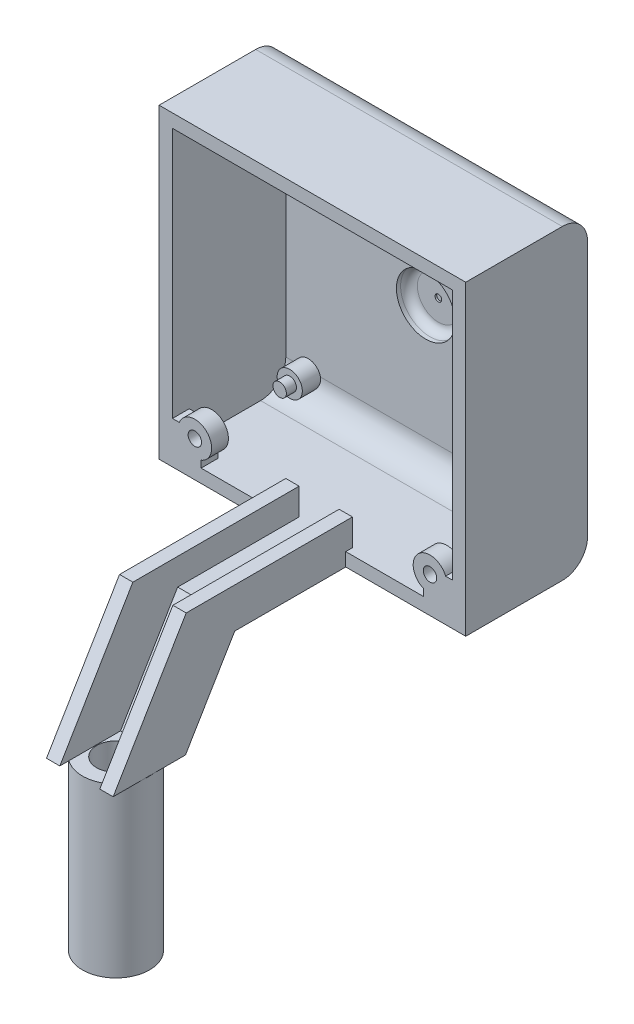
SolidWorks part; units mm, degrees
ref_plane "Front Plane" through (0, 0, 0) normal (0, 0, 1) x (1, 0, 0)
ref_plane "Top Plane" through (0, 0, 0) normal (0, 1, 0) x (1, 0, 0)
ref_plane "Right Plane" through (0, 0, 0) normal (1, 0, 0) x (0, 0, -1)
sketch "Sketch1" plane through (0, 0, 0) normal (0, 0, 1) x (1, 0, 0)
  line L0 (0, 0) -> (0, -36.5125)
  line L1 (0, -36.5125) -> (36.5125, -36.5125)
  line L2 (36.5125, -36.5125) -> (36.5125, 0)
  line L3 (36.5125, 0) -> (0, 0)
  dimension "D1" = 36.5125
extrude "Extrude1" add sketch "Sketch1" along normal blind 1
sketch "Sketch2" plane through (0, 0, 1) normal (0, 0, 1) x (1, 0, 0)
  line L0 (1.5875, -1.5875) -> (34.925, -1.5875)
  line L3 (34.925, -34.925) -> (34.925, -1.5875)
  line L4 (1.5875, -34.925) -> (1.5875, -1.5875)
  line L5 (34.925, -34.925) -> (1.5875, -34.925)
  line L6 (0, 0) -> (36.5125, 0)
  line L7 (36.5125, -36.5125) -> (36.5125, 0) construction
  line L8 (36.5125, 0) -> (0, 0) construction
  line L9 (36.5125, 0) -> (36.5125, -36.5125)
  line L10 (0, -36.5125) -> (36.5125, -36.5125) construction
  line L11 (36.5125, -36.5125) -> (0, -36.5125)
  line L12 (0, 0) -> (0, -36.5125) construction
  line L13 (0, -36.5125) -> (0, 0)
extrude "Extrude2" add sketch "Sketch2" along normal blind 13.5
fillet "Fillet7" radius 3 4 edges at (18.2562, 0, 0) (18.2562, -36.5125, 0) (18.2562, -1.5875, 1) (18.2562, -34.925, 1)
sketch "Sketch5" plane through (0, 0, 1) normal (0, 0, 1) x (1, 0, 0)
  line L0 (1.5875, -1.5875) -> (34.925, -34.925) construction
  line L1 (34.925, -1.5875) -> (1.5875, -34.925) construction
  line L2 (34.925, -34.925) -> (34.925, -1.5875) construction
  circle A0 centre (4.2562, -4.2562) radius 1.5
  circle A1 centre (32.2563, -4.2562) radius 1.5
  circle A2 centre (4.2562, -32.2563) radius 1.5
  circle A3 centre (32.2563, -32.2563) radius 1.5
  point P8 (4.2562, -32.2563)
  point P9 (18.2562, -18.2562)
  point P10 (32.2563, -32.2563)
  point P11 (4.2562, -4.2562)
  point P12 (32.2563, -4.2562)
  dimension "D1" = 14
  dimension "D2" = 14
  dimension "D3" = 14
  dimension "D4" = 14
extrude "Extrude5" add sketch "Sketch5" along normal blind 2.2
sketch "Sketch6" plane through (0, 0, 3.2) normal (0, 0, 1) x (1, 0, 0)
  circle A0 centre (4.2562, -32.2563) radius 0.8
  circle A1 centre (32.2563, -32.2563) radius 0.8
  circle A2 centre (4.2562, -4.2562) radius 0.8
  circle A3 centre (32.2563, -4.2562) radius 0.8
extrude "Extrude6" add sketch "Sketch6" along normal blind 1.2
sketch "Sketch7" plane through (0, 0, 1) normal (0, 0, 1) x (1, 0, 0)
  line L0 (0, 0) -> (36.5125, -36.5125) construction
  line L1 (36.5125, 0) -> (0, -36.5125) construction
  line L2 (0, -36.5125) -> (36.5125, -36.5125) construction
  circle A0 centre (18.2562, -18.2562) radius 4.5
  point P9 (18.2562, -18.2562)
extrude "Extrude7" add sketch "Sketch7" against normal blind 2.5
sketch "Sketch8" plane through (0, 0, 1) normal (0, 0, 1) x (1, 0, 0)
  line L0 (0, 0) -> (36.5125, -36.5125) construction
  line L1 (36.5125, 0) -> (0.5068, -36.3499) construction
  circle A0 centre (18.2562, -18.2562) radius 3.5
  point P6 (18.3431, -18.3431)
extrude "Extrude9" cut sketch "Sketch8" against normal blind 1.5
fillet "Fillet8" radius 1 1 edges at (22.7562, -18.2562, -1.5)
fillet "Fillet10" radius 1 1 edges at (21.7562, -18.2562, -0.5)
sketch "Sketch9" plane through (0, 0, -0.5) normal (0, 0, 1) x (1, 0, 0)
  circle A0 centre (18.2562, -18.2562) radius 0.4
extrude "Extrude10" cut sketch "Sketch9" against normal blind 0.2
sketch "Sketch10" plane through (0, 0, 14.5) normal (0, 0, 1) x (1, 0, 0)
  line L0 (-4.7625, -31.5125) -> (46.0375, -31.5125) construction
  line L1 (5, -15.875) -> (5, -49.2125) construction
  line L2 (31.5125, -15.875) -> (31.5125, -49.2125) construction
  line L3 (31.5125, -34.1128) -> (31.5125, -36.5126)
  line L4 (31.5125, -36.5126) -> (36.5125, -36.5125)
  line L5 (36.5125, -36.5125) -> (36.5125, -31.5125)
  line L6 (36.5125, -36.5125) -> (36.5125, 0) construction
  line L7 (36.5125, -31.5125) -> (34.1128, -31.5125)
  line L8 (2.3997, -31.5125) -> (0, -31.5125)
  line L9 (0, 0) -> (0, -36.5125) construction
  line L10 (0, -31.5125) -> (0, -36.5125)
  line L11 (0, -36.5125) -> (5, -36.5125)
  line L12 (0, -36.5125) -> (36.5125, -36.5125) construction
  line L13 (5, -36.5125) -> (5, -34.1128)
  circle A0 centre (4.2562, -32.2563) radius 2 construction
  circle A1 centre (32.2563, -32.2563) radius 2 construction
  circle A2 centre (4.2562, -32.2563) radius 0.8
  circle A3 centre (32.2563, -32.2563) radius 0.8
  arc A4 (2.3997, -31.5125) -> (5, -34.1128) centre (4.2562, -32.2563) cw
  arc A5 (34.1128, -31.5125) -> (31.5125, -34.1128) centre (32.2563, -32.2563) ccw
  dimension "D1" = 5
  dimension "D2" = 5
  dimension "D3" = 5
extrude "Extrude11" add sketch "Sketch10" against normal blind 2
sketch "Sketch11" plane through (0, 0, 14.5) normal (0, 0, 1) x (1, 0, 0)
  line L0 (14.2875, -36.5125) -> (14.2875, -31.75)
  line L1 (14.2875, -31.75) -> (15.875, -31.75)
  line L2 (22.225, -31.75) -> (22.225, -36.5125)
  line L3 (0, -36.5125) -> (31.5125, -36.5125) construction
  line L4 (22.225, -36.5125) -> (14.2875, -36.5125)
  line L5 (15.875, -31.75) -> (15.875, -33.3375)
  line L6 (20.6375, -33.3375) -> (20.6375, -34.925)
  line L7 (34.925, -34.925) -> (1.5875, -34.925) construction
  line L8 (20.6375, -34.925) -> (15.875, -34.925)
  line L9 (5, -34.925) -> (31.5125, -34.925) construction
  line L10 (15.875, -33.3375) -> (15.875, -34.925)
  line L11 (22.225, -31.75) -> (20.6375, -31.75)
  line L12 (20.6375, -31.75) -> (20.6375, -33.3375)
  point P0 (4.2562, -32.2563)
  point P1 (32.2563, -32.2563)
extrude "Extrude12" add sketch "Sketch11" along normal blind 19 and the other way blind 0.8
sketch "Sketch13" plane through (14.2875, 0, 0) normal (-1, 0, 0) x (0, 0, 1)
  line L0 (33.5, -31.75) -> (25.5, -36.5125)
  line L1 (14.5, -36.5125) -> (33.5, -36.5125) construction
  line L2 (25.5, -36.5125) -> (33.5, -36.5125)
  line L3 (33.5, -36.5125) -> (33.5, -31.75)
extrude "Extrude13" cut sketch "Sketch13" against normal through all
sketch "Sketch14" plane through (0, -38.1668, 22.7212) normal (0, -0.8593, 0.5115) x (1, 0, 0)
  line L0 (22.225, 12.5443) -> (22.225, 5.1443)
  line L1 (15.875, 12.5443) -> (14.2875, 12.5443) construction
  line L2 (14.2875, 12.5443) -> (14.2875, 3.234) construction
  line L6 (22.225, 3.234) -> (22.225, 12.5443) construction
  line L7 (22.225, 12.5443) -> (20.6375, 12.5443)
  line L8 (20.6375, 12.5443) -> (20.6375, 6.3374)
  line L9 (20.6375, 6.3374) -> (15.875, 6.3374)
  line L10 (15.875, 6.3374) -> (15.875, 12.5443) construction
  line L11 (20.6375, 6.3374) -> (15.875, 6.3374) construction
  line L12 (15.875, 6.3374) -> (15.875, 12.5443)
  line L13 (15.875, 12.5443) -> (14.2875, 12.5443)
  line L14 (22.225, 5.1443) -> (14.2875, 5.1443)
  line L15 (14.2875, 5.1443) -> (14.2875, 12.5443)
extrude "Extrude14" add sketch "Sketch14" along normal blind 17
sketch "Sketch15" plane through (14.2875, 0, 0) normal (-1, 0, 0) x (0, 0, 1)
  line L0 (42.196, -46.3575) -> (33.584, -46.3575)
  line L1 (35.8375, -50.1428) -> (27.1414, -35.5353) construction
  line L2 (33.584, -46.3575) -> (35.8375, -50.1428)
  line L3 (35.8375, -50.1428) -> (42.196, -46.3575)
extrude "Extrude15" cut sketch "Sketch15" against normal through all
sketch "Sketch16" plane through (0, -46.3575, 0) normal (0, -1, 0) x (1, 0, 0)
  line L0 (14.2875, 42.196) -> (22.225, 33.584) construction
  line L1 (14.2875, 33.584) -> (22.225, 42.196) construction
  line L2 (0, 14.5) -> (14.2875, 14.5) construction
  circle A0 centre (18.2563, 37.89) radius 2.3
  circle A1 centre (18.2563, 37.89) radius 4
  dimension "D1" = 23.39
extrude "Extrude16" add sketch "Sketch16" along normal blind 20
sketch "Sketch17" plane through (0, 0, 14.5) normal (0, 0, 1) x (1, 0, 0)
  line L0 (14.2875, -36.5125) -> (22.225, -36.5125)
  line L1 (0, -36.5125) -> (14.2875, -36.5125) construction
  line L2 (22.225, -36.5125) -> (31.5125, -36.5125) construction
  line L3 (14.2875, -34.925) -> (14.2875, -36.5125)
  line L4 (34.925, -34.925) -> (1.5875, -34.925) construction
  line L5 (22.225, -34.925) -> (14.2875, -34.925)
  line L6 (5, -34.925) -> (14.2875, -34.925) construction
  line L7 (22.225, -34.925) -> (22.225, -36.5125)
extrude "Extrude17" add sketch "Sketch17" along normal blind 13.5
